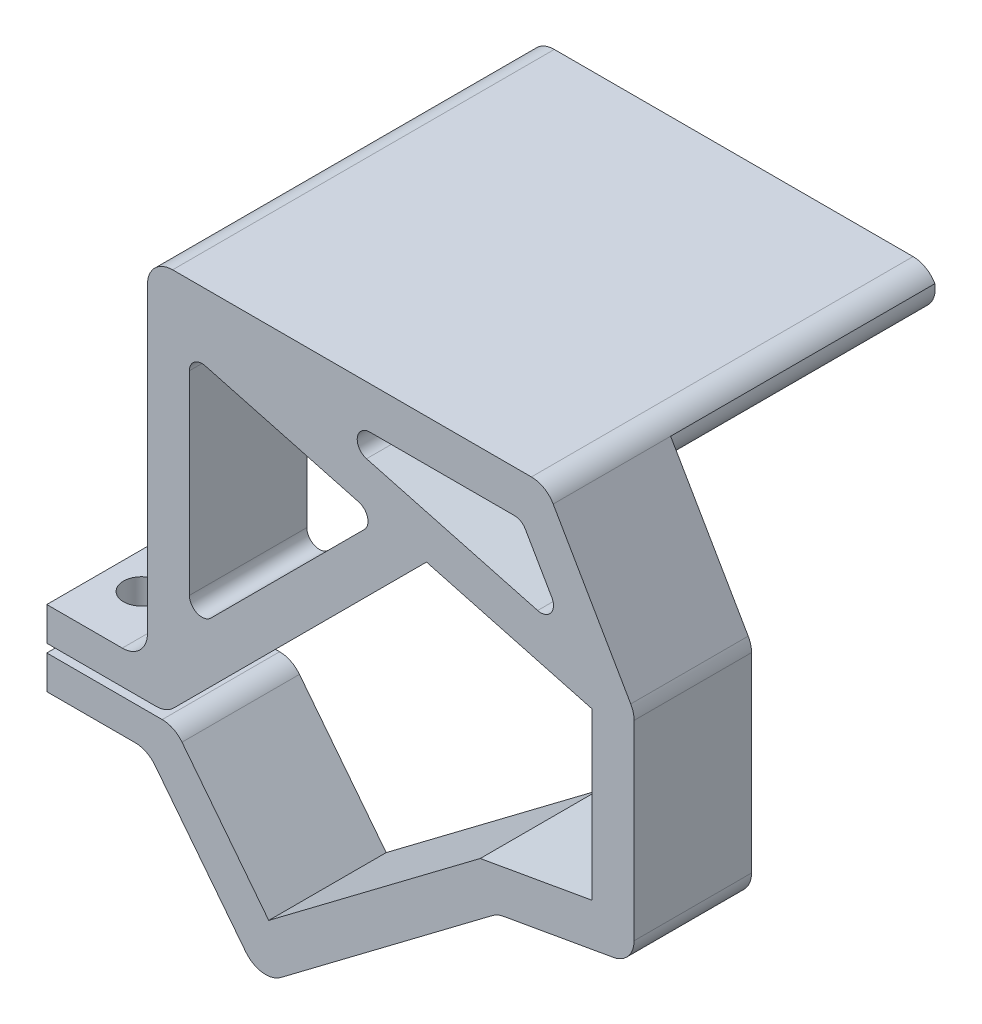
SolidWorks part; units mm, degrees
ref_plane "前视基准面" through (0, 0, 0) normal (0, 0, 1) x (1, 0, 0)
ref_plane "上视基准面" through (0, 0, 0) normal (0, 1, 0) x (1, 0, 0)
ref_plane "右视基准面" through (0, 0, 0) normal (1, 0, 0) x (0, 0, -1)
sketch "Sketch1" plane through (0, 0, 0) normal (0, 0, 1) x (1, 0, 0)
  line L0 (-1.2413, 13.8567) -> (-14.2506, 13.8567)
  line L1 (-14.2506, 13.8567) -> (-14.2506, 17.8567)
  line L2 (-14.2506, 17.8567) -> (-5.2506, 17.8567)
  line L3 (-2.2506, 20.8567) -> (-2.2506, 59.9107)
  line L4 (-3.7138, 8.8567) -> (-14.2506, 8.8567)
  line L5 (-14.2506, 8.8567) -> (-14.2506, 12.8567)
  line L6 (-14.2506, 12.8567) -> (-3.0933, 12.8567)
  line L7 (-3.0933, 12.8567) -> (-0.4939, 12.8567)
  line L8 (-0.2506, 80.9107) -> (-0.2506, 59.9107) construction
  line L24 (1.198, 12.564) -> (10.994, 0.0257) construction
  line L25 (30.1981, 44.0535) -> (15.6079, 29.4632) construction
  line L27 (13.7806, -0.3412) -> (29.1076, 11.2086) construction
  line L28 (37.895, 17.5574) -> (49.1104, 19.535) construction
  line L29 (50.7629, 21.5043) -> (50.7629, 38.0438) construction
  line L30 (49.2807, 39.9754) -> (32.1297, 44.571) construction
  line L31 (1.8701, 11.7037) -> (12.2071, -1.5269)
  line L32 (31.0145, 44.8698) -> (15.6079, 29.4632)
  line L33 (15.6079, 29.4632) -> (0.8801, 14.7354)
  line L34 (12.2071, -1.5269) -> (37.4222, 17.4741)
  line L35 (37.4222, 17.4741) -> (50.7629, 19.8264)
  line L36 (50.7629, 19.8264) -> (50.7629, 39.5783)
  line L37 (50.7629, 39.5783) -> (31.0145, 44.8698)
  line L38 (-0.2506, 59.9107) -> (45.2494, 59.9107)
  line L39 (45.2494, 59.9107) -> (55.3609, 42.3969)
  line L40 (55.7629, 40.8969) -> (55.7629, 18.1482)
  line L41 (53.2838, 15.1938) -> (40.1819, 12.8835)
  line L42 (38.8974, 12.325) -> (13.6465, -6.7029)
  line L43 (9.477, -6.154) -> (-1.3498, 7.7037)
  line L47 (-2.2506, 59.9107) -> (-0.2506, 59.9107)
  line L48 (45.9513, 48.6949) -> (42.7956, 54.1607)
  line L49 (41.4966, 54.9107) -> (24.2535, 54.9107)
  line L50 (23.8653, 51.9618) -> (44.2641, 46.496)
  line L51 (23.6006, 44.527) -> (5.31, 26.2364)
  line L52 (2.7494, 27.2971) -> (2.7494, 50.4886)
  line L53 (4.6376, 51.9375) -> (22.9282, 47.0365)
  arc A0 (5.31, 26.2364) -> (2.7494, 27.2971) centre (4.2494, 27.2971) cw
  arc A1 (2.7494, 50.4886) -> (4.6376, 51.9375) centre (4.2494, 50.4886) cw
  arc A2 (23.6006, 44.527) -> (22.9282, 47.0365) centre (22.5399, 45.5877) ccw
  arc A3 (24.2535, 54.9107) -> (23.8653, 51.9618) centre (24.2535, 53.4107) ccw
  arc A4 (42.7956, 54.1607) -> (41.4966, 54.9107) centre (41.4966, 53.4107) ccw
  arc A5 (45.9513, 48.6949) -> (44.2641, 46.496) centre (44.6523, 47.9449) cw
  arc A6 (-5.2506, 17.8567) -> (-2.2506, 20.8567) centre (-5.2506, 20.8567) ccw
  arc A7 (-1.3498, 7.7037) -> (-3.7138, 8.8567) centre (-3.7138, 5.8567) ccw
  arc A8 (13.6465, -6.7029) -> (9.477, -6.154) centre (11.8411, -4.307) cw
  arc A9 (40.1819, 12.8835) -> (38.8974, 12.325) centre (40.7029, 9.9291) ccw
  arc A10 (55.7629, 18.1482) -> (53.2838, 15.1938) centre (52.7629, 18.1482) cw
  arc A11 (55.3609, 42.3969) -> (55.7629, 40.8969) centre (52.7629, 40.8969) cw
  arc A12 (-1.2413, 13.8567) -> (0.8801, 14.7354) centre (-1.2413, 16.8567) ccw
  arc A13 (-0.4939, 12.8567) -> (1.8701, 11.7037) centre (-0.4939, 9.8567) cw
  point P57 (-2.2506, 17.8567)
  point P60 (-2.2506, 8.8567)
  dimension "D11" = 1.5
  dimension "D19" = 3
  dimension "D20" = 3
  dimension "D1" = 5
  dimension "D2" = 5
  dimension "D3" = 5
  dimension "D4" = 5
  dimension "D5" = 5
  dimension "D6" = 5
  dimension "D7" = 5
  dimension "D8" = 5
  dimension "D9" = 5
  dimension "D10" = 4
  dimension "D12" = 4
  dimension "D13" = 1
  dimension "D14" = 12
  dimension "D15" = 12
  dimension "D16" = 5
  dimension "D17" = 2
  dimension "D18" = 120
extrude "Boss-Extrude1" add sketch "Sketch1" against normal up to vertex (14 mm away)
fillet "Fillet1" radius 3 2 edges at (-2.2506, 59.9107, -7) (45.2494, 59.9107, -7)
sketch "Sketch2" plane through (0, 8.8567, 0) normal (0, -1, 0) x (1, 0, 0)
  line L0 (-9.741, -6.9999) -> (32.259, -6.9999) construction
  line L1 (-14.2506, -14) -> (-14.2506, 0) construction
  circle A0 centre (-9.9506, -6.9999) radius 2.15
  dimension "D1" = 4.3
  dimension "D2" = 4.3
extrude "Cut-Extrude1" cut sketch "Sketch2" against normal blind 20
sketch "Sketch3" plane through (0, 0, -14) normal (0, 0, -1) x (-1, 0, 0)
  line L0 (-43.5173, 59.9107) -> (-0.7494, 59.9107) construction
  line L1 (-43.5173, 59.9107) -> (-0.7494, 59.9107)
  line L2 (-41.4966, 54.9107) -> (-24.2535, 54.9107) construction
  line L3 (-48.1361, 54.9107) -> (2.2506, 54.9107)
  line L4 (2.2506, 56.9107) -> (2.2506, 20.8567) construction
  line L5 (-55.3609, 42.3969) -> (-46.1154, 58.4107) construction
  line L6 (-46.1154, 58.4107) -> (-48.1361, 54.9107)
  line L7 (2.2506, 56.9107) -> (2.2506, 54.9107)
  arc A0 (2.2506, 56.9107) -> (-0.7494, 59.9107) centre (-0.7494, 56.9107) ccw construction
  arc A1 (-43.5173, 59.9107) -> (-46.1154, 58.4107) centre (-43.5173, 56.9107) ccw construction
  arc A2 (2.2506, 56.9107) -> (-0.7494, 59.9107) centre (-0.7494, 56.9107) ccw
  arc A3 (-43.5173, 59.9107) -> (-46.1154, 58.4107) centre (-43.5173, 56.9107) ccw
extrude "Boss-Extrude2" add sketch "Sketch3" along normal up to vertex (31.5 mm away)
fillet "Fillet2" radius 3 2 edges at (-2.2506, 54.9107, -29.75) (48.1361, 54.9107, -29.75)
sketch "Sketch4" plane through (0, 0, -14) normal (0, 0, -1) x (-1, 0, 0)
  line L0 (2.2506, 56.9107) -> (2.2506, 20.8567) construction
  line L1 (-2.7477, 45.9553) -> (2.2506, 45.9553)
  line L2 (-2.7477, 45.9553) -> (-2.7477, 40.9553)
  line L3 (-2.7477, 40.9553) -> (2.2506, 40.9553)
  line L4 (2.2506, 45.9553) -> (2.2506, 40.9553)
  line L5 (-9.2741, 30.2005) -> (-5.7386, 26.665)
  line L6 (-9.2741, 30.2005) -> (-12.8097, 26.665)
  line L7 (-5.7386, 26.665) -> (-9.2741, 23.1295)
  line L8 (-12.8097, 26.665) -> (-9.2741, 23.1295)
  line L9 (-5.31, 26.2364) -> (-23.6006, 44.527) construction
  line L11 (-0.8801, 14.7354) -> (-31.0145, 44.8698) construction
  dimension "D1" = 5
  dimension "D2" = 5
extrude "Boss-Extrude3" add sketch "Sketch4" along normal blind 7
sketch "Sketch5" plane through (0, 0, -21) normal (0, 0, -1) x (-1, 0, 0)
  line L0 (-12.8097, 26.665) -> (-9.2741, 23.1295)
  line L1 (2.2506, 45.9553) -> (-7.7494, 45.9553)
  line L2 (2.2506, 45.9553) -> (2.2506, 40.9553)
  line L3 (2.2506, 40.9553) -> (-7.7494, 40.9553)
  line L4 (-7.7494, 45.9553) -> (-7.7494, 40.9553)
  line L5 (-12.8097, 26.665) -> (-5.7386, 33.7361)
  line L6 (-9.2741, 23.1295) -> (-2.2031, 30.2005)
  line L7 (-5.7386, 33.7361) -> (-2.2031, 30.2005)
  dimension "D1" = 10
  dimension "D2" = 10
extrude "Boss-Extrude4" add sketch "Sketch5" along normal blind 4
fillet "Fillet3" radius 1 8 edges at (7.5064, 28.4328, -21) (2.7477, 43.4553, -21) (11.0419, 28.4328, -14) (7.5064, 24.8972, -14) (11.0419, 24.8972, -25) (0.2485, 40.9553, -14) (0.2485, 45.9553, -14) (-2.2506, 43.4553, -25)
